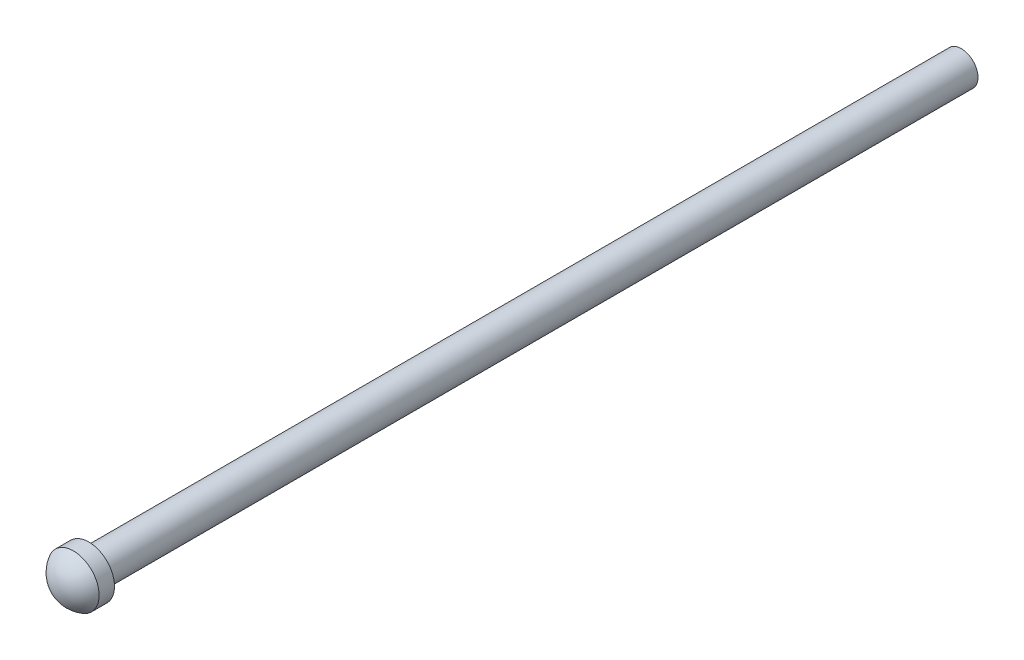
SolidWorks part; units mm, degrees
ref_plane "Front Plane" through (0, 0, 0) normal (0, 0, 1) x (1, 0, 0)
ref_plane "Top Plane" through (0, 0, 0) normal (0, 1, 0) x (1, 0, 0)
ref_plane "Right Plane" through (0, 0, 0) normal (1, 0, 0) x (0, 0, -1)
sketch "Sketch1" plane through (0, 0, 0) normal (0, 0, 1) x (1, 0, 0)
  circle A2 centre (5, 60) radius 3.25
  circle A3 centre (5, 60) radius 3.25
  dimension "D1" = 0.25
sketch "Sketch2" plane through (0, 0, 0) normal (1, 0, 0) x (0, 0, -1)
  line L0 (0, 0) -> (170, 0) construction
  line L1 (0, 0) -> (170, 0)
  line L2 (0, 0) -> (170, 0)
sweep "Sweep1" add profiles "Sketch1" path "Sketch2"
sketch "Sketch4" plane through (0, 0, 0) normal (0, 0, 1) x (1, 0, 0)
  circle A0 centre (5, 60) radius 5
  arc A1 (5, 55) -> (0, 60) centre (5, 60) ccw construction
extrude "Boss-Extrude1" add sketch "Sketch4" along normal blind 3
dome "Dome1" faces to dome 1 distance 3 reverse direction no elliptical dome no face at (10, 60, 3) parameters "D1"=3
